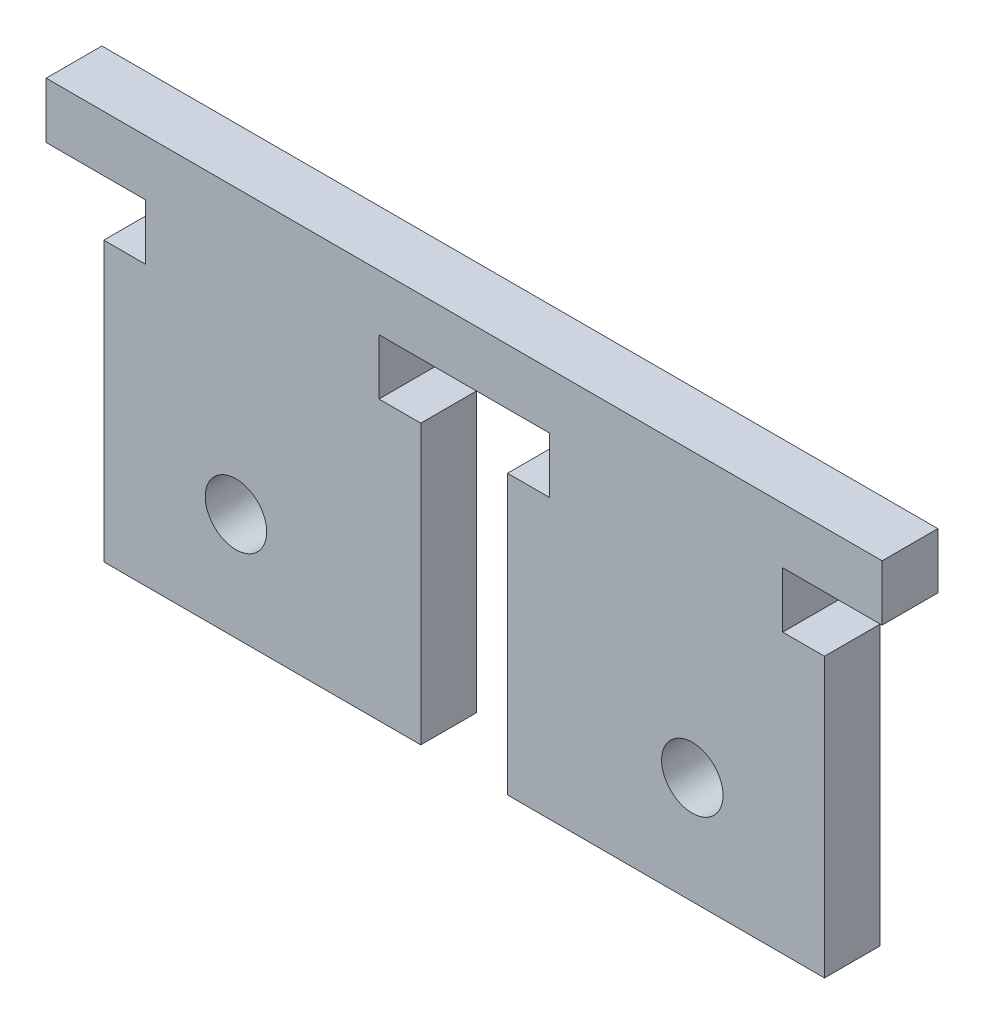
SolidWorks part; units mm, degrees
material "AISI 4130 Steel, annealed at 865C"
ref_plane "X-Y Datum" through (0, 0, 0) normal (0, 0, 1) x (1, 0, 0)
ref_plane "X-Z Datum" through (0, 0, 0) normal (0, 1, 0) x (1, 0, 0)
ref_plane "Y-Z Datum" through (0, 0, 0) normal (1, 0, 0) x (0, 0, -1)
sketch "Sketch3" plane through (0, 0, 0) normal (0, 0, 1) x (1, 0, 0)
  line L1 (-47.625, -30.48) -> (47.625, -30.48)
  line L2 (-47.625, -30.48) -> (-47.625, 30.48)
  line L3 (-47.625, 30.48) -> (47.625, 30.48)
  line L4 (47.625, -30.48) -> (47.625, 30.48)
  line L5 (-47.625, -30.48) -> (47.625, 30.48) construction
  line L6 (-47.625, 30.48) -> (47.625, -30.48) construction
  point P0 (0, 0)
  dimension "D1" = 95.25
  dimension "D2" = 60.96
extrude "Boss-Extrude1" add sketch "Sketch3" along normal blind 6.35
sketch "Sketch4" plane through (0, 0, 6.35) normal (0, 0, 1) x (1, 0, 0)
  line L0 (-47.625, 15.24) -> (-41.0616, 15.24)
  line L1 (-47.625, 30.48) -> (-47.625, -30.48) construction
  line L2 (-41.0616, 15.24) -> (-4.5491, 15.24)
  line L3 (-4.5491, 15.24) -> (4.5491, 15.24)
  line L4 (4.5491, 15.24) -> (41.0616, 15.24)
  line L5 (41.0616, 15.24) -> (47.625, 15.24)
  line L6 (47.625, -30.48) -> (47.625, 30.48) construction
  line L7 (0, 15.24) -> (0, -30.48) construction
  line L8 (-41.0616, 15.24) -> (-47.625, 15.24)
  line L9 (-41.0616, 15.24) -> (-41.0616, -30.48)
  line L10 (-41.0616, -30.48) -> (-47.625, -30.48)
  line L11 (-47.625, 15.24) -> (-47.625, -30.48)
  line L12 (-47.625, -30.48) -> (47.625, -30.48) construction
  line L13 (-1.5875, -16.0071) -> (1.5875, -16.0071)
  line L14 (-1.5875, -16.0071) -> (-1.5875, 0.7671)
  line L17 (-4.5491, 15.24) -> (4.5491, 15.24)
  line L19 (-4.9418, -30.48) -> (4.9418, -30.48)
  line L20 (-4.9418, -30.48) -> (-4.9418, 15.24)
  line L25 (-4.9418, 15.24) -> (4.9418, 15.24)
  line L26 (4.9418, -30.48) -> (4.9418, 15.24)
  line L27 (41.0616, 15.24) -> (47.625, 15.24)
  line L28 (41.0616, 15.24) -> (41.0616, -30.48)
  line L29 (41.0616, -30.48) -> (47.625, -30.48)
  line L31 (-4.9418, -30.48) -> (4.9418, 15.24) construction
  line L32 (-4.9418, 15.24) -> (4.9418, -30.48) construction
  line L33 (-1.5875, 0.7671) -> (1.5875, 0.7671)
  line L34 (1.5875, -16.0071) -> (1.5875, 0.7671)
  line L35 (-1.5875, -16.0071) -> (1.5875, 0.7671) construction
  line L36 (-1.5875, 0.7671) -> (1.5875, -16.0071) construction
  point P15 (0, -7.62)
  point P20 (0, -7.62)
  point P30 (0, 0)
  line M5 (47.625, -30.48) -> (47.625, 30.48)
  line M7 (-47.625, 30.48) -> (-47.625, -30.48)
  line M8 (-47.625, -30.48) -> (47.625, -30.48)
  dimension "D1" = 6.5634
  dimension "D2" = 36.5125
  dimension "D3" = 6.5634
  dimension "D4" = 36.5125
  dimension "D5" = 9.8837
  dimension "D6" = 45.72
  dimension "D7" = 3.175
  dimension "D9" = 45.72
extrude "Cut-Extrude1" cut sketch "Sketch4" against normal blind 6.35 contours L9 L0 M7 M8 | L5 L28 M8 M5 | L19 L26 L4 L3 L2 L20 L34 L13 L14 L33 | L13 L34 L33 L14 region at (-44.3433, -7.62, 6.35) region at (-4.7455, 14.7722, 6.35) region at (44.3433, -7.62, 6.35) region at (0, -7.62, 6.35)
sketch "Sketch5" plane through (0, 0, 6.35) normal (0, 0, 1) x (1, 0, 0)
  line L9 (-41.0616, 15.24) -> (-4.9418, 15.24)
  line L26 (-41.0616, 15.24) -> (-36.2991, 15.24)
  line L27 (-41.0616, 15.24) -> (-41.0616, 8.89)
  line L28 (-41.0616, 8.89) -> (-36.2991, 8.89)
  line L29 (-36.2991, 15.24) -> (-36.2991, 8.89)
  line L30 (-4.9418, 15.24) -> (-9.7043, 15.24)
  line L31 (-4.9418, 15.24) -> (-4.9418, 8.89)
  line L32 (-4.9418, 8.89) -> (-9.7043, 8.89)
  line L33 (-9.7043, 15.24) -> (-9.7043, 8.89)
  line M5 (-41.0616, 15.24) -> (-41.0616, -30.48)
  line M7 (-4.9418, -30.48) -> (-4.9418, 15.24)
  dimension "D1" = 6.35
  dimension "D2" = 4.7625
extrude "Cut-Extrude2" cut sketch "Sketch5" against normal blind 6.35 contours L29 L9 L28 M5 | L9 L33 L32 M7 region at (-7.3231, 12.065, 6.35) region at (-38.6804, 12.065, 6.35)
mirror "Mirror1" about plane through (0, 0, 0) normal (1, 0, 0) of "Cut-Extrude2"
sketch "Sketch8" [suppressed] plane through (0, 15.24, 0) normal (0, -1, 0) x (1, 0, 0)
  line L0 (-9.525, 3.175) -> (9.525, 3.175) construction
  line L1 (-9.525, 0) -> (-9.525, 6.35) construction
  line L2 (9.525, 0) -> (9.525, 6.35) construction
  line L3 (-4.7625, 6.35) -> (4.7625, 6.35) construction
  line L4 (-4.7625, 0) -> (4.7625, 0)
  line L5 (-4.7625, 0) -> (-4.7625, 6.35)
  line L6 (-4.7625, 6.35) -> (4.7625, 6.35)
  line L7 (4.7625, 0) -> (4.7625, 6.35)
  line L8 (-4.7625, 0) -> (4.7625, 6.35) construction
  line L9 (-4.7625, 6.35) -> (4.7625, 0) construction
  point P6 (0, 3.175)
  line M3 (-4.7625, 0) -> (4.7625, 0)
  dimension "D1" = 4.7625
extrude "Cut-Extrude3" [suppressed] cut sketch "Sketch8" against normal blind 1.5875 contours L7 L0 L5 M3
sketch "Sketch9" plane through (0, 30.48, 0) normal (0, 1, 0) x (1, 0, 0)
  line L1 (-47.625, 0) -> (47.625, 0)
  line L2 (-47.625, 0) -> (-47.625, -6.35)
  line L3 (-47.625, -6.35) -> (47.625, -6.35)
  line L4 (47.625, 0) -> (47.625, -6.35)
extrude "Cut-Extrude6" cut sketch "Sketch9" against normal blind 8.89
sketch "Sketch10" plane through (0, 0, 6.35) normal (0, 0, 1) x (1, 0, 0)
  line L0 (0, 0) -> (0, -30.2463) construction
  line L1 (-26, -10.6279) -> (26, -10.6279) construction
  circle A1 centre (-26, -10.6279) radius 3.3015
  circle A3 centre (26, -10.6279) radius 3.3015
  point P2 (26, -10.6279)
  point P10 (-26, -10.6279)
  point P21 (-26, -10.6279)
  point P23 (26, -10.6279)
  dimension "D2" = 6.603
  dimension "D1" = 52
sketch "Sketch11" plane through (0, -30.48, 0) normal (0, -1, 0) x (1, 0, 0)
  line L1 (-41.0616, 6.35) -> (41.0616, 6.35)
  line L2 (-41.0616, 6.35) -> (-41.0616, 0)
  line L3 (-41.0616, 0) -> (41.0616, 0)
  line L4 (41.0616, 6.35) -> (41.0616, 0)
  point P6 (0, 0)
  point P7 (-41.0616, 6.35)
extrude "Cut-Extrude9" cut sketch "Sketch11" against normal blind 7.62
hole_wizard "M6 Clearance Hole2" positions "Sketch10" profile "Sketch12" hole size "M6" standard "ANSI Metric" end condition through all
sketch "Sketch12" plane through (26, -10.6279, 6.35) normal (1, 0, 0) x (0, -1, 0)
  line L0 (0, 0) -> (0, 6.35)
  line L1 (0, 6.35) -> (3.5, 6.35)
  line L2 (3.5, 6.35) -> (3.5, 0)
  line L5 (3.5, 0) -> (0, 0)
  line L11 (0, -6.35) -> (0, 107.95) construction
  dimension "Thru Hole Dia." = 7
  dimension "Thru Hole Depth" = 6.35
